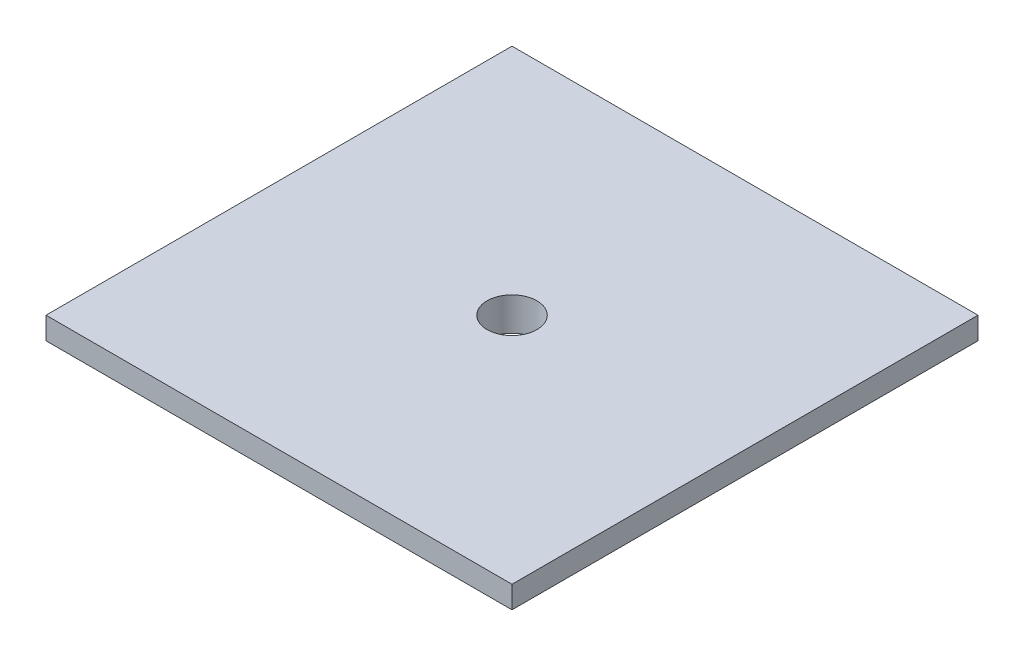
SolidWorks part; units mm, degrees
ref_plane "Front Plane" through (0, 0, 0) normal (0, 0, 1) x (1, 0, 0)
ref_plane "Top Plane" through (0, 0, 0) normal (0, 1, 0) x (1, 0, 0)
ref_plane "Right Plane" through (0, 0, 0) normal (1, 0, 0) x (0, 0, -1)
sketch "Sketch2" plane through (0, 0, 0) normal (0, 1, 0) x (1, 0, 0)
  line L1 (-105, -105) -> (105, -105)
  line L2 (-105, -105) -> (-105, 105)
  line L3 (-105, 105) -> (105, 105)
  line L4 (105, -105) -> (105, 105)
  line L5 (-105, -105) -> (105, 105) construction
  line L6 (-105, 105) -> (105, -105) construction
  point P0 (0, 0)
  dimension "D1" = 210
  dimension "D2" = 210
extrude "Boss-Extrude1" add sketch "Sketch2" along normal blind 10
sketch "Sketch3" plane through (0, 0, 0) normal (0, -1, 0) x (1, 0, 0)
  line L1 (-90, -90) -> (90, -90)
  line L2 (-90, -90) -> (-90, 90)
  line L3 (-90, 90) -> (90, 90)
  line L4 (90, -90) -> (90, 90)
  line L5 (-90, -90) -> (90, 90) construction
  line L6 (-90, 90) -> (90, -90) construction
  point P0 (0, 0)
  dimension "D1" = 180
  dimension "D2" = 180
extrude "Boss-Extrude2" add sketch "Sketch3" along normal blind 5 draft 1
sketch "Sketch4" plane through (0, 10, 0) normal (0, 1, 0) x (1, 0, 0)
  circle A0 centre (0, 0) radius 11.25
  dimension "D1" = 22.5
extrude "Cut-Extrude1" cut sketch "Sketch4" against normal up to surface (15 mm away) up to face at (0, -5, 0)
